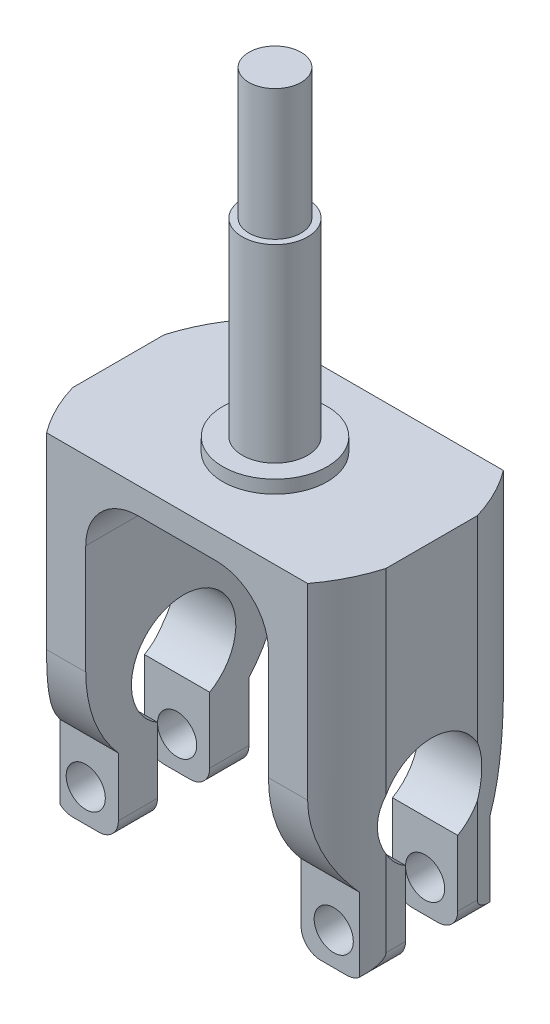
SolidWorks part; units mm, degrees
ref_plane "前视基准面" through (0, 0, 0) normal (0, 0, 1) x (1, 0, 0)
ref_plane "上视基准面" through (0, 0, 0) normal (0, 1, 0) x (1, 0, 0)
ref_plane "右视基准面" through (0, 0, 0) normal (1, 0, 0) x (0, 0, -1)
sketch "草图1" plane through (0, 0, 0) normal (0, 1, 0) x (1, 0, 0)
  circle A0 centre (0, 0) radius 12.5
  dimension "D1" = 25
extrude "凸台-拉伸1" add sketch "草图1" against normal blind 27
sketch "草图2" plane through (0, -27, 0) normal (0, -1, 0) x (-1, 0, 0)
  line L0 (-15.7613, 0) -> (20.3286, 0) construction
  line L1 (-10, 7.5) -> (10, 7.5)
  line L2 (-10, -7.5) -> (10, -7.5)
  arc A1 (-10, -7.5) -> (10, -7.5) centre (0, 0) ccw
  arc A2 (10, 7.5) -> (-10, 7.5) centre (0, 0) ccw
  dimension "D2" = 12.5
  dimension "D1" = 15
extrude "切除-拉伸1" cut sketch "草图2" against normal blind 37
sketch "草图3" plane through (0, 0, 0) normal (0, 1, 0) x (1, 0, 0)
  line L0 (0, 0) -> (0, 9.8429) construction
  line L2 (-12, 3.5) -> (-12, -3.5)
  line L4 (12, 3.5) -> (12, -3.5)
  arc A2 (-12, 3.5) -> (-12, -3.5) centre (0, 0) ccw
  arc A3 (12, -3.5) -> (12, 3.5) centre (0, 0) ccw
  dimension "D3" = 12.5
  dimension "D1" = 24
extrude "切除-拉伸2" cut sketch "草图3" against normal blind 43 from offset 10
sketch "草图4" plane through (0, 0, 7.5) normal (0, 0, 1) x (1, 0, 0)
  line L0 (-10, -27) -> (10, -27) construction
  line L1 (-7, -27) -> (7, -27)
  line L2 (-7, -27) -> (-7, -2)
  line L3 (-7, -2) -> (7, -2)
  line L4 (7, -27) -> (7, -2)
  line L5 (0, 0) -> (0, -32.6337) construction
  line L6 (-10, 0) -> (10, 0) construction
  dimension "D1" = 14
  dimension "D2" = 2
extrude "切除-拉伸3" cut sketch "草图4" against normal blind 30
fillet "圆角1" radius 4 2 edges at (-7, -2, 0) (7, -2, 0)
ref_plane "基准面1" through (0, 1, 0) normal (0, 1, 0) x (1, 0, 0)
sketch "草图5" plane through (0, 1, 0) normal (0, 1, 0) x (1, 0, 0)
  circle A0 centre (0, 0) radius 4
  dimension "D1" = 8
sketch "草图7" plane through (0, 0, 0) normal (0, 1, 0) x (1, 0, 0)
  circle A0 centre (0, 0) radius 4
  dimension "D1" = 8
loft "放样2" add profiles "草图7", "草图5" connector at (3.2002, 0, -2.3997) connector at (3.0936, 1, -2.5357)
sketch "草图8" plane through (-12, 0, 0) normal (-1, 0, 0) x (0, 0, 1)
  line L0 (0, 0) -> (0, -20.4765) construction
  line L2 (3.5, -27) -> (-3.5, -27) construction
  line L3 (-2, -27) -> (2, -27)
  line L4 (-2, -27) -> (-2, -20.4641)
  line L6 (2, -27) -> (2, -20.4641)
  arc A0 (2, -20.4641) -> (-2, -20.4641) centre (0, -17) ccw
  dimension "D1" = 8
  dimension "D2" = 17
  dimension "D3" = 4
extrude "切除-拉伸4" cut sketch "草图8" against normal blind 34
sketch "草图9" plane through (-12, 0, 0) normal (-1, 0, 0) x (0, 0, 1)
  line L0 (5, -21) -> (5, -27)
  line L1 (3.5, -27) -> (7.5, -27) construction
  line L2 (5, -27) -> (7.5, -27)
  line L3 (7.5, -27) -> (7.5, -21)
  line L4 (7.5, 0) -> (7.5, -27) construction
  line L5 (7.5, -21) -> (5, -21)
  line L6 (0, -17) -> (0, -29.0445) construction
  line L7 (2, -27) -> (2, -20.4641) construction
  line L8 (-5, -27) -> (-7.5, -27)
  line L9 (-7.5, -27) -> (-7.5, -21)
  line L10 (-7.5, -21) -> (-5, -21)
  line L11 (-5, -21) -> (-5, -27)
  circle A0 centre (0, -17) radius 6.4031 construction
  dimension "D1" = 4
  dimension "D2" = 3
extrude "切除-拉伸5" cut sketch "草图9" against normal blind 34
sketch "草图10" plane through (0, 0, 5) normal (0, 0, 1) x (1, 0, 0)
  line L1 (11.4564, -27) -> (7, -27) construction
  line L2 (0, 0) -> (0, -33.0612) construction
  circle A0 centre (-9.5, -24.5) radius 1.5
  circle A1 centre (9.5, -24.5) radius 1.5
  dimension "D3" = 3
  dimension "D4" = 2.5
  dimension "D5" = 19
extrude "切除-拉伸6" cut sketch "草图10" against normal blind 34
fillet "圆角3" radius 1.5 8 edges at (-12, -27, 2.75) (-12, -27, -2.75) (-7, -27, -3.5) (-7, -27, 3.5) (7, -27, -3.5) (7, -27, 3.5) (12, -27, 2.75) (12, -27, -2.75)
sketch "草图11" plane through (0, 1, 0) normal (0, 1, 0) x (1, 0, 0)
  circle A0 centre (0, 0) radius 2.5
  dimension "D1" = 5
extrude "凸台-拉伸2" add sketch "草图11" along normal blind 14.5
sketch "草图12" plane through (0, 15.5, 0) normal (0, 1, 0) x (1, 0, 0)
  circle A0 centre (0, 0) radius 2
  dimension "D1" = 4
extrude "凸台-拉伸3" add sketch "草图12" along normal blind 10
cosmetic thread "装饰螺纹线1" parameters "D1"=8, "D2"=2.5
fillet "圆角4" radius 10 4 edges at (8.5, -21, 7.5) (8.5, -21, -7.5) (-8.5, -21, -7.5) (-8.5, -21, 7.5)
